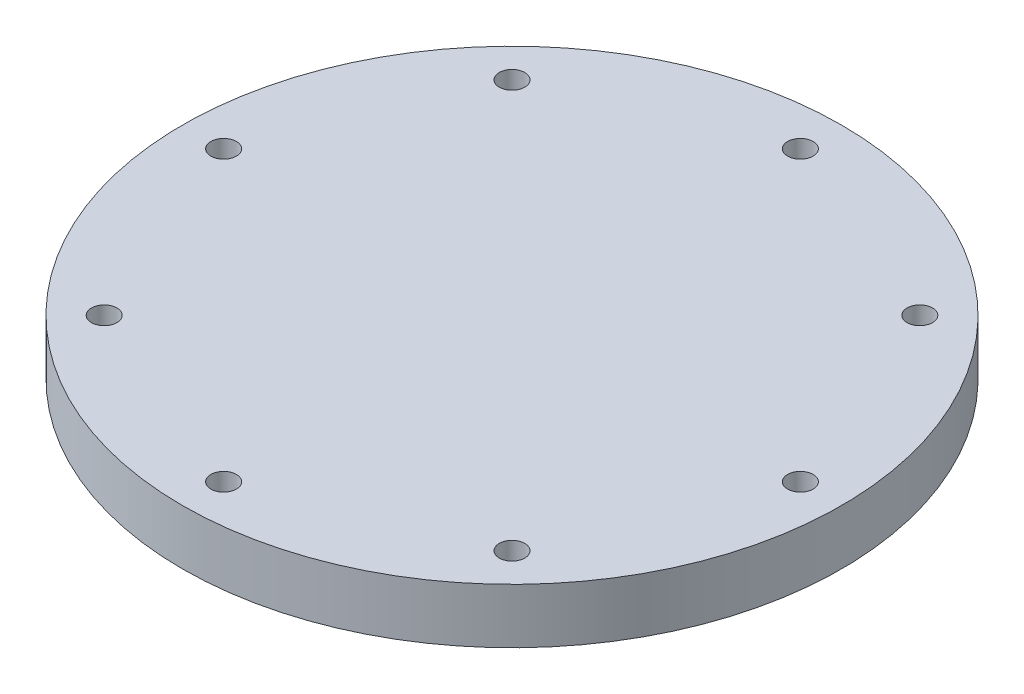
SolidWorks part; units mm, degrees
ref_plane "Front Plane" through (0, 0, 0) normal (0, 0, 1) x (1, 0, 0)
ref_plane "Top Plane" through (0, 0, 0) normal (0, 1, 0) x (1, 0, 0)
ref_plane "Right Plane" through (0, 0, 0) normal (1, 0, 0) x (0, 0, -1)
sketch "Sketch1" plane through (0, 0, 0) normal (0, 1, 0) x (1, 0, 0)
  circle A0 centre (0, 0) radius 38.1
  dimension "D1" = 76.2
extrude "Boss-Extrude1" add sketch "Sketch1" along normal blind 6.35
sketch "Sketch2" plane through (0, 0, 0) normal (0, -1, 0) x (1, 0, 0)
  circle A0 centre (0, 0) radius 33.3375
  circle A1 centre (0, 33.3375) radius 0.762
  dimension "D1" = 66.675
hole_wizard "CBORE for #4 Button Head Cap Screw1" positions "Sketch5" profile "Sketch4" counterbore size "#4" standard "ANSI Inch" end condition through all
sketch "Sketch5" plane through (0, 0, 0) normal (0, -1, 0) x (-1, 0, 0)
  point P0 (0, -33.3375)
sketch "Sketch4" plane through (0, 0, 33.3375) normal (1, 0, 0) x (0, 0, -1)
  line L0 (0, 0) -> (0, 6.35)
  line L1 (0, 6.35) -> (1.4732, 6.35)
  line L3 (1.4732, 6.35) -> (1.4732, 2.8448)
  line L4 (1.4732, 2.8448) -> (2.413, 2.8448)
  line L5 (2.413, 2.8448) -> (2.413, 0)
  line L7 (2.413, 0) -> (0, 0)
  line L11 (0, -6.35) -> (0, 107.95) construction
  dimension "Thru Hole Dia." = 2.9464
  dimension "Thru Hole Depth" = 6.35
  dimension "C'Bore Dia." = 4.826
  dimension "C'Bore Depth" = 2.8448
pattern_circular "CirPattern1" count 8 over 360 about axis through (0, 0, 0) along (0, 1, 0) of "CBORE for #4 Button Head Cap Screw1"
sketch "Sketch6" plane through (0, 6.35, 0) normal (0, 1, 0) x (1, 0, 0)
  circle A0 centre (0, 0) radius 28.575
  dimension "D1" = 57.15
sketch "Sketch7" plane through (0, 0, 0) normal (0, -1, 0) x (1, 0, 0)
  circle A0 centre (0, 12.7) radius 0.3937
  dimension "D1" = 0.7874
  dimension "D2" = 12.7
